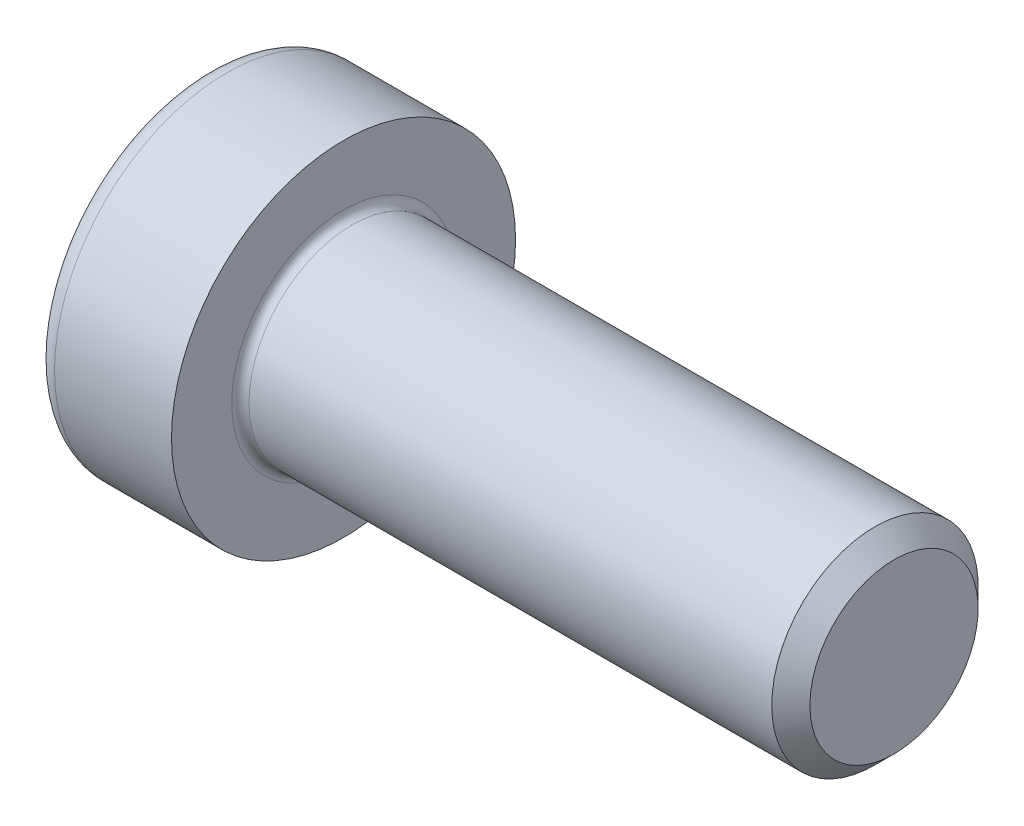
SolidWorks part; units mm, degrees
revolve "Base-Revolve" add sketch "BodySke"
sketch "BodySke" plane through (0, 0, 0) normal (0, 0, 1) x (1, 0, 0)
  line L0 (0, 0) -> (0, 5)
  line L1 (0, 5) -> (4, 5)
  line L2 (4, 5) -> (4, 3)
  line L3 (4, 3) -> (19.4455, 3)
  line L4 (20, 2.4455) -> (20, 0)
  line L5 (20, 0) -> (0, 0)
  line L6 (-31.75, 0) -> (127, 0) construction
  line L8 (20, 2.4455) -> (19.4455, 3)
  line L10 (20, -2.4455) -> (19.4455, -3) construction
  line L11 (5, 4.525) -> (5, -1.825) construction
  line L12 (4, 4.525) -> (4, -1.825) construction
  line L13 (-40, 4.525) -> (-40, -1.825) construction
  dimension "Diameter" = 6
  dimension "Head_dia" = 10
cosmetic thread "ThreadCosmetic"
fillet "Fillet1" radius 0.25 1 edges at (4, 0, 3)
fillet "Fillet2" radius 0.6 1 edges at (0, 0, 5)
ref_plane "Plane1" through (0, 0, 0) normal (0, 0, 1) x (1, 0, 0)
ref_plane "Plane2" through (0, 0, 0) normal (0, 1, 0) x (1, 0, 0)
ref_plane "Plane3" through (0, 0, 0) normal (1, 0, 0) x (0, 0, -1)
sketch "HexSke" plane through (0, 0, 0) normal (-1, 0, 0) x (0, 0.5, 0.866)
  line L0 (1.4434, 2.5) -> (-1.4434, 2.5)
  line L1 (-1.4434, 2.5) -> (-2.8868, 0)
  line L2 (1.4434, 2.5) -> (2.8868, 0)
  line L3 (1.4434, -2.5) -> (2.8868, 0)
  line L4 (1.4434, -2.5) -> (-1.4434, -2.5)
  line L5 (-1.4434, -2.5) -> (-2.8868, 0)
  dimension "D1" = 2.5
  dimension "D2" = 2.5
extrude "Hex" cut sketch "HexSke" against normal blind 2.5
sketch "PilotSke" plane through (0, 0, 0) normal (0, 0, 1) x (1, 0, 0)
  line L0 (0, 2.5) -> (2.5, 2.5)
  line L1 (2.5, 2.5) -> (3.0774, 1.5)
  line L2 (-31.75, 0) -> (127, 0) construction
  line L3 (5.866, 0) -> (0, 0)
  line L4 (0, 0) -> (0, 2.5)
  line L5 (3.0774, 1.5) -> (5, 1.5)
  line L6 (0, 0) -> (47.625, 0) construction
  line L7 (5, 1.5) -> (5.866, 0)
  dimension "D1" = 2.5
  dimension "D2" = 60
revolve "Hex-PreBroach" cut sketch "PilotSke" angle 360 about L6
sketch "ThdSchSke" plane through (0, 0, 0) normal (0, 0, 1) x (1, 0, 0)
  line L0 (7, -2.4455) -> (6.6117, -3)
  line L1 (7, -2.4455) -> (7.3883, -3)
  line L2 (7.3883, -3) -> (7.3883, -3.75)
  line L3 (-3.175, 0) -> (5.1513, 0) construction
  line L4 (0, 4.4) -> (0, -4.4) construction
  line L5 (7.3883, -3.75) -> (6.6117, -3.75)
  line L6 (6.6117, -3.75) -> (6.6117, -3)
  dimension "Diameter" = 6
  dimension "Thread_minor" = 4.891
  dimension "Start" = 7
revolve "ThreadSchematic" [suppressed] cut sketch "ThdSchSke" angle 360 about L3
pattern_linear "ThdSchPat" [suppressed]
equation "\"D2@HexSke\" = \"Hex_size@HexSke\" / 2"
equation "\"D1@HexSke\" = \"Hex_size@HexSke\" / 2"
equation "\"D1@PilotSke\" = \"Hex_size@HexSke\" / 2"
equation "\"Thread_minor@ThreadCosmetic\"  =  \"Minor_dia@BodySke\""
equation "\"Depth@PilotSke\" =  \"Key_eng@Hex\""
equation "\"Thread_length@ThreadCosmetic\" = ((sgn( (\"Length@BodySke\" - \"Advance@BodySke\" * 3.0) - \"Thread_nom@BodySke\" )-1)*( (\"Length@BodySke\" - \"Advance@BodySke\" * 3.0) - \"Thread_nom@BodySke\" ))/-2+ \"Thread_nom@BodySke\""
equation "\"Thread_minor@ThdSchSke\" = \"Minor_dia@BodySke\""
equation "\"Diameter@ThdSchSke\" = \"Diameter@BodySke\""
equation "\"Overcut@ThdSchSke\" = \"Diameter@BodySke\" * 1.25"
equation "\"Start@ThdSchSke\" = \"Head_ht@BodySke\" + \"Length@BodySke\" - \"Thread_length@ThreadCosmetic\"  '---Non-countersunk---"
equation "\"Num_threads@ThdSchPat\" = int( \"Thread_length@ThreadCosmetic\" / \"Advance@BodySke\" + 0.999 )  + 1"
equation "\"Advance@ThdSchPat\" = \"Thread_length@ThreadCosmetic\" /  (\"Num_threads@ThdSchPat\" - 1) 'relax it"
equation "\"Num_threads@ThdSchPat\" = \"Num_threads@ThdSchPat\" - sgn( \"Num_threads@ThdSchPat\" - 1) '---chamfered tips only---"
